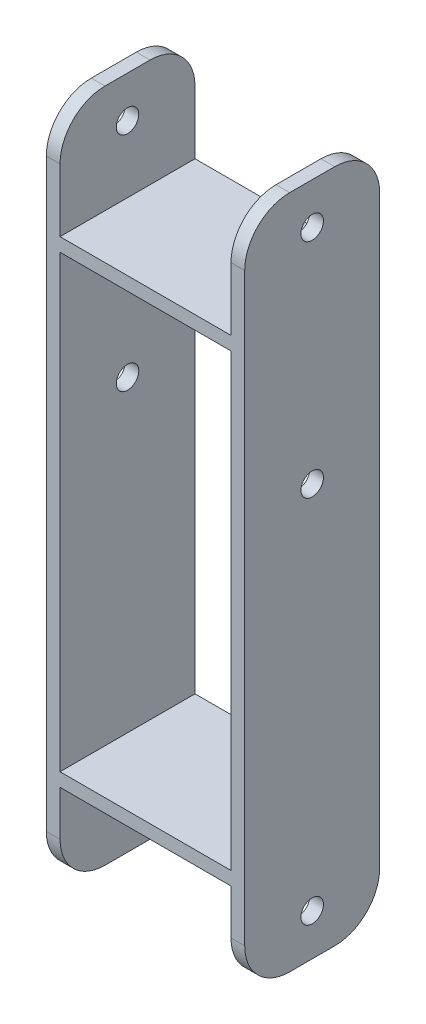
SolidWorks part; units mm, degrees
ref_plane "Front Plane" through (0, 0, 0) normal (0, 0, 1) x (1, 0, 0)
ref_plane "Top Plane" through (0, 0, 0) normal (0, 1, 0) x (1, 0, 0)
ref_plane "Right Plane" through (0, 0, 0) normal (1, 0, 0) x (0, 0, -1)
sketch "Sketch1" plane through (0, 0, 0) normal (0, 0, 1) x (1, 0, 0)
  line L0 (0, 26.1905) -> (0, -22.5714) construction
  line L1 (-22.0476, 100) -> (-19, 100)
  line L2 (-22.0476, 100) -> (-22.0476, -50)
  line L3 (-22.0476, -50) -> (-19, -50)
  line L4 (-19, 100) -> (-19, -50)
  line L5 (22.0476, -50) -> (19, -50)
  line L6 (19, 100) -> (19, -50)
  line L7 (22.0476, 100) -> (22.0476, -50)
  line L8 (22.0476, 100) -> (19, 100)
  line L10 (-19, 76) -> (19, 76)
  line L11 (-19, 76) -> (-19, 73)
  line L12 (-19, 73) -> (19, 73)
  line L13 (19, 76) -> (19, 73)
  line L14 (-19, -27) -> (19, -27)
  line L15 (-19, -27) -> (-19, -30)
  line L16 (-19, -30) -> (19, -30)
  line L17 (19, -27) -> (19, -30)
  dimension "D1" = 38
  dimension "D2" = 150
  dimension "D3" = 3.0476
  dimension "D4" = 50
  dimension "D5" = 3
  dimension "D6" = 3
  dimension "D7" = 100
  dimension "D8" = 20
extrude "Boss-Extrude1" add sketch "Sketch1" along normal mid plane 30 contours L4 L1 L2 L3 | L7 L8 L6 L5 | L10 L13 L12 L11 | L14 L17 L16 L15 region at (-20.5238, 25, 0) region at (20.5238, 25, 0)
fillet "Fillet1" radius 10 8 edges at (-20.5238, -50, -15) (20.5238, -50, -15) (20.5238, -50, 15) (-20.5238, -50, 15) (-20.5238, 100, 15) (-20.5238, 100, -15) (20.5238, 100, -15) (20.5238, 100, 15)
sketch "Sketch2" plane through (22.0476, 0, 0) normal (1, 0, 0) x (0, 0, -1)
  circle A0 centre (0, 41.4396) radius 2.5
  circle A1 centre (0, -40.7478) radius 2.5
  dimension "D1" = 5
  dimension "D2" = 5
extrude "Cut-Extrude1" cut sketch "Sketch2" against normal blind 61
sketch "Sketch3" plane through (22.0476, 0, 0) normal (1, 0, 0) x (0, 0, -1)
  circle A0 centre (0, 90.8245) radius 2.5
  dimension "D1" = 5
extrude "Cut-Extrude2" cut sketch "Sketch3" against normal blind 55
